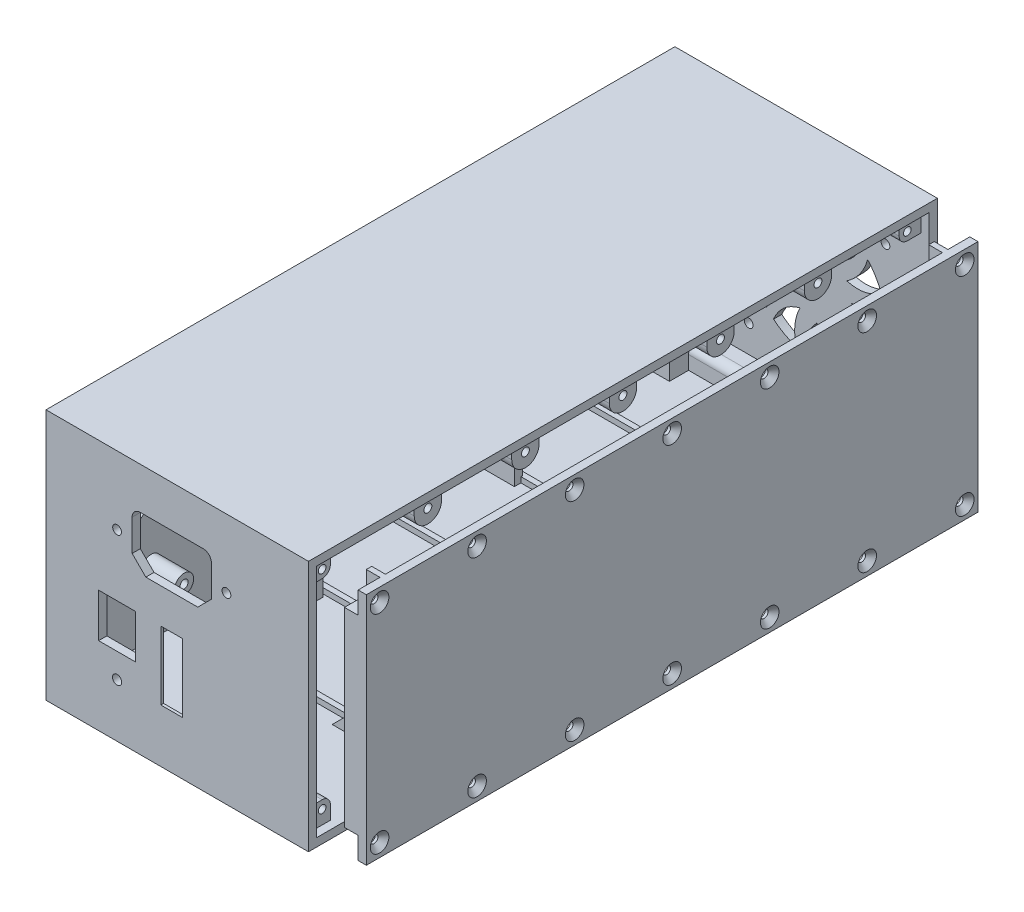
SolidWorks part; units mm, degrees
ref_plane "Front Plane" through (0, 0, 0) normal (0, 0, 1) x (1, 0, 0)
ref_plane "Top Plane" through (0, 0, 0) normal (0, 1, 0) x (1, 0, 0)
ref_plane "Right Plane" through (0, 0, 0) normal (1, 0, 0) x (0, 0, -1)
sketch "Sketch1" plane through (0, 0, 0) normal (1, 0, 0) x (0, 0, -1)
  line L1 (115, 46) -> (-115, 46)
  line L2 (115, 46) -> (115, -46)
  line L3 (115, -46) -> (-115, -46)
  line L4 (-115, 46) -> (-115, -46)
  line L5 (115, 46) -> (-115, -46) construction
  line L6 (115, -46) -> (-115, 46) construction
  point P0 (0, 0)
  dimension "D1" = 92
  dimension "D2" = 230
extrude "Boss-Extrude1" add sketch "Sketch1" along normal blind 3
sketch "Sketch2" plane through (3, 0, 0) normal (1, 0, 0) x (0, 0, -1)
  line L0 (-112, 43) -> (-112, -43)
  line L1 (-112, -43) -> (112, -43)
  line L2 (112, -43) -> (112, 43)
  line L3 (112, 43) -> (-112, 43)
  line L4 (-115, 46) -> (-115, -46)
  line L5 (-115, -46) -> (115, -46)
  line L6 (115, -46) -> (115, 46)
  line L7 (115, 46) -> (-115, 46)
  line L8 (-115, 46) -> (-115, -46)
  line L9 (-115, -46) -> (115, -46)
  line L10 (115, -46) -> (115, 46)
  line L11 (115, 46) -> (-115, 46)
  dimension "D1" = 0
  dimension "D2" = 3
extrude "Boss-Extrude2" add sketch "Sketch2" along normal blind 93
sketch "Sketch3" plane through (0, 0, 0) normal (-1, 0, 0) x (0, 0, 1)
  line L0 (-115, 0) -> (115, 0) construction
  line L1 (-115, -46) -> (-115, 46) construction
  line L2 (115, 46) -> (115, -46) construction
  line L3 (0, 46) -> (0, -46) construction
  line L4 (-115, 46) -> (115, 46) construction
  line L5 (115, -46) -> (-115, -46) construction
  line L6 (26.5, -7.75) -> (18.5, -7.75)
  line L7 (11.5, 7.75) -> (3.5, 7.75)
  line L8 (11.5, 7.75) -> (11.5, -7.75)
  line L9 (11.5, -7.75) -> (3.5, -7.75)
  line L10 (3.5, 7.75) -> (3.5, -7.75)
  line L11 (11.5, 7.75) -> (3.5, -7.75) construction
  line L12 (11.5, -7.75) -> (3.5, 7.75) construction
  line L13 (26.5, 7.75) -> (26.5, -7.75)
  line L14 (26.5, 7.75) -> (18.5, 7.75)
  line L15 (18.5, 7.75) -> (18.5, -7.75)
  line L16 (41.5, -7.75) -> (33.5, -7.75)
  line L17 (41.5, 7.75) -> (41.5, -7.75)
  line L18 (41.5, 7.75) -> (33.5, 7.75)
  line L19 (33.5, 7.75) -> (33.5, -7.75)
  line L20 (56.5, -7.75) -> (48.5, -7.75)
  line L21 (56.5, 7.75) -> (56.5, -7.75)
  line L22 (56.5, 7.75) -> (48.5, 7.75)
  line L23 (48.5, 7.75) -> (48.5, -7.75)
  line L24 (71.5, -7.75) -> (63.5, -7.75)
  line L25 (71.5, 7.75) -> (71.5, -7.75)
  line L26 (71.5, 7.75) -> (63.5, 7.75)
  line L27 (63.5, 7.75) -> (63.5, -7.75)
  line L28 (11.5, -7.75) -> (3.5, -7.75)
  line L29 (11.5, 7.75) -> (11.5, -7.75)
  line L30 (11.5, 7.75) -> (3.5, 7.75)
  line L31 (3.5, 7.75) -> (3.5, -7.75)
  line L32 (26.5, -7.75) -> (18.5, -7.75)
  line L33 (26.5, 7.75) -> (26.5, -7.75)
  line L34 (26.5, 7.75) -> (18.5, 7.75)
  line L35 (18.5, 7.75) -> (18.5, -7.75)
  line L36 (41.5, -7.75) -> (33.5, -7.75)
  line L37 (41.5, 7.75) -> (41.5, -7.75)
  line L38 (41.5, 7.75) -> (33.5, 7.75)
  line L39 (33.5, 7.75) -> (33.5, -7.75)
  line L40 (56.5, -7.75) -> (48.5, -7.75)
  line L41 (56.5, 7.75) -> (56.5, -7.75)
  line L42 (56.5, 7.75) -> (48.5, 7.75)
  line L43 (48.5, 7.75) -> (48.5, -7.75)
  line L44 (-3.5, -7.75) -> (-11.5, -7.75)
  line L45 (-3.5, 7.75) -> (-3.5, -7.75)
  line L46 (-3.5, 7.75) -> (-11.5, 7.75)
  line L47 (-11.5, 7.75) -> (-11.5, -7.75)
  line L48 (11.5, -7.75) -> (3.5, -7.75)
  line L49 (11.5, 7.75) -> (11.5, -7.75)
  line L50 (11.5, 7.75) -> (3.5, 7.75)
  line L51 (3.5, 7.75) -> (3.5, -7.75)
  line L52 (26.5, -7.75) -> (18.5, -7.75)
  line L53 (26.5, 7.75) -> (26.5, -7.75)
  line L54 (26.5, 7.75) -> (18.5, 7.75)
  line L55 (18.5, 7.75) -> (18.5, -7.75)
  line L56 (41.5, -7.75) -> (33.5, -7.75)
  line L57 (41.5, 7.75) -> (41.5, -7.75)
  line L58 (41.5, 7.75) -> (33.5, 7.75)
  line L59 (33.5, 7.75) -> (33.5, -7.75)
  line L60 (-18.5, -7.75) -> (-26.5, -7.75)
  line L61 (-18.5, 7.75) -> (-18.5, -7.75)
  line L62 (-18.5, 7.75) -> (-26.5, 7.75)
  line L63 (-26.5, 7.75) -> (-26.5, -7.75)
  line L64 (-3.5, -7.75) -> (-11.5, -7.75)
  line L65 (-3.5, 7.75) -> (-3.5, -7.75)
  line L66 (-3.5, 7.75) -> (-11.5, 7.75)
  line L67 (-11.5, 7.75) -> (-11.5, -7.75)
  line L68 (11.5, -7.75) -> (3.5, -7.75)
  line L69 (11.5, 7.75) -> (11.5, -7.75)
  line L70 (11.5, 7.75) -> (3.5, 7.75)
  line L71 (3.5, 7.75) -> (3.5, -7.75)
  line L72 (26.5, -7.75) -> (18.5, -7.75)
  line L73 (26.5, 7.75) -> (26.5, -7.75)
  line L74 (26.5, 7.75) -> (18.5, 7.75)
  line L75 (18.5, 7.75) -> (18.5, -7.75)
  line L76 (-33.5, -7.75) -> (-41.5, -7.75)
  line L77 (-33.5, 7.75) -> (-33.5, -7.75)
  line L78 (-33.5, 7.75) -> (-41.5, 7.75)
  line L79 (-41.5, 7.75) -> (-41.5, -7.75)
  line L80 (-18.5, -7.75) -> (-26.5, -7.75)
  line L81 (-18.5, 7.75) -> (-18.5, -7.75)
  line L82 (-18.5, 7.75) -> (-26.5, 7.75)
  line L83 (-26.5, 7.75) -> (-26.5, -7.75)
  line L84 (-3.5, -7.75) -> (-11.5, -7.75)
  line L85 (-3.5, 7.75) -> (-3.5, -7.75)
  line L86 (-3.5, 7.75) -> (-11.5, 7.75)
  line L87 (-11.5, 7.75) -> (-11.5, -7.75)
  line L88 (11.5, -7.75) -> (3.5, -7.75)
  line L89 (11.5, 7.75) -> (11.5, -7.75)
  line L90 (11.5, 7.75) -> (3.5, 7.75)
  line L91 (3.5, 7.75) -> (3.5, -7.75)
  line L92 (-48.5, -7.75) -> (-56.5, -7.75)
  line L93 (-48.5, 7.75) -> (-48.5, -7.75)
  line L94 (-48.5, 7.75) -> (-56.5, 7.75)
  line L95 (-56.5, 7.75) -> (-56.5, -7.75)
  line L96 (-33.5, -7.75) -> (-41.5, -7.75)
  line L97 (-33.5, 7.75) -> (-33.5, -7.75)
  line L98 (-33.5, 7.75) -> (-41.5, 7.75)
  line L99 (-41.5, 7.75) -> (-41.5, -7.75)
  line L100 (-18.5, -7.75) -> (-26.5, -7.75)
  line L101 (-18.5, 7.75) -> (-18.5, -7.75)
  line L102 (-18.5, 7.75) -> (-26.5, 7.75)
  line L103 (-26.5, 7.75) -> (-26.5, -7.75)
  line L104 (-3.5, -7.75) -> (-11.5, -7.75)
  line L105 (-3.5, 7.75) -> (-3.5, -7.75)
  line L106 (-3.5, 7.75) -> (-11.5, 7.75)
  line L107 (-11.5, 7.75) -> (-11.5, -7.75)
  line L108 (-3.5, -7.75) -> (-11.5, -7.75)
  line L109 (-3.5, 7.75) -> (-3.5, -7.75)
  line L110 (-3.5, 7.75) -> (-11.5, 7.75)
  line L111 (-11.5, 7.75) -> (-11.5, -7.75)
  line L112 (-18.5, -7.75) -> (-26.5, -7.75)
  line L113 (-18.5, 7.75) -> (-18.5, -7.75)
  line L114 (-18.5, 7.75) -> (-26.5, 7.75)
  line L115 (-26.5, 7.75) -> (-26.5, -7.75)
  line L116 (-33.5, -7.75) -> (-41.5, -7.75)
  line L117 (-33.5, 7.75) -> (-33.5, -7.75)
  line L118 (-33.5, 7.75) -> (-41.5, 7.75)
  line L119 (-41.5, 7.75) -> (-41.5, -7.75)
  line L120 (-48.5, -7.75) -> (-56.5, -7.75)
  line L121 (-48.5, 7.75) -> (-48.5, -7.75)
  line L122 (-48.5, 7.75) -> (-56.5, 7.75)
  line L123 (-56.5, 7.75) -> (-56.5, -7.75)
  line L124 (-63.5, -7.75) -> (-71.5, -7.75)
  line L125 (-63.5, 7.75) -> (-63.5, -7.75)
  line L126 (-63.5, 7.75) -> (-71.5, 7.75)
  line L127 (-71.5, 7.75) -> (-71.5, -7.75)
  circle A0 centre (84.6037, 0) radius 1
  point P12 (7.5, 0)
  dimension "D6" = 2
  dimension "D1" = 7.5
  dimension "D2" = 15.5
  dimension "D3" = 8
  dimension "D4" = 5
  dimension "D5" = 6
extrude "Cut-Extrude1" cut sketch "Sketch3" against normal up to surface (3 mm away) contours L126 L127 L124 L125 | L94 L95 L92 L93 | L78 L79 L76 L77 | L62 L63 L60 L61 | L46 L47 L44 L45 | L7 L10 L9 L8 | L14 L15 L6 L13 | L18 L19 L16 L17 | L22 L23 L20 L21 | L26 L27 L24 L25 | A0 region at (0, 0, 22.5) region at (0, 0, 7.5) region at (0, 0, 37.5) region at (0, 0, 52.5) region at (0, 0, 67.5) region at (0, 0, -7.5) region at (0, 0, -22.5) region at (0, 0, -37.5) region at (0, 0, -52.5) region at (0, 0, -67.5) region at (0, 0, 84.6037) up to face at (3, 0, 0)
sketch "Sketch4" plane through (96, 0, 0) normal (1, 0, 0) x (0, 0, -1)
  line L0 (0, 43) -> (0, -43) construction
  line L1 (112, 43) -> (-112, 43) construction
  line L2 (-112, -43) -> (112, -43) construction
  line L3 (-112, 43) -> (-112, -43) construction
  line L4 (-104, 38) -> (-104, 43)
  line L5 (-104, 43) -> (-112, 43)
  line L6 (-112, 43) -> (-112, 35)
  line L7 (-112, 35) -> (-107, 35)
  line L8 (0, 0) -> (-112, 0) construction
  line L9 (-107, -35) -> (-112, -35)
  line L10 (-112, 43) -> (-112, -43) construction
  line L11 (-112, -35) -> (-112, -43)
  line L12 (-104, -38) -> (-104, -43)
  line L13 (-104, -43) -> (-112, -43)
  line L14 (104, -43) -> (112, -43)
  line L15 (112, -35) -> (112, -43)
  line L16 (107, -35) -> (112, -35)
  line L17 (112, 35) -> (107, 35)
  line L18 (112, 43) -> (112, 35)
  line L19 (104, 43) -> (112, 43)
  line L20 (104, 38) -> (104, 43)
  line L21 (104, -38) -> (104, -43)
  circle A0 centre (-107, 38) radius 1.4
  circle A1 centre (-107, -38) radius 1.4
  arc A2 (-104, 38) -> (-107, 35) centre (-107, 38) cw
  arc A3 (-107, -35) -> (-104, -38) centre (-107, -38) cw
  arc A4 (107, -35) -> (104, -38) centre (107, -38) ccw
  circle A5 centre (107, -38) radius 1.4
  arc A6 (104, 38) -> (107, 35) centre (107, 38) ccw
  circle A7 centre (107, 38) radius 1.4
  dimension "D5" = 2.8
  dimension "D6" = 3
  dimension "D1" = 5
  dimension "D2" = 5
  dimension "D3" = 5
  dimension "D4" = 5
extrude "Boss-Extrude3" add sketch "Sketch4" against normal up to surface (93 mm away) from offset 3 up to face at (3, 0, -67.5) offset against normal yes
sketch "Sketch5" plane through (93, 0, 0) normal (1, 0, 0) x (0, 0, -1)
  circle A0 centre (-107, -38) radius 1.4 construction
  circle A1 centre (107, -38) radius 1.4 construction
  circle A2 centre (107, 38) radius 1.4 construction
  circle A3 centre (-107, 38) radius 1.4 construction
  circle A4 centre (-107, -38) radius 1.4
  circle A5 centre (107, -38) radius 1.4
  circle A6 centre (107, 38) radius 1.4
  circle A7 centre (-107, 38) radius 1.4
extrude "Boss-Extrude4" add sketch "Sketch5" against normal up to surface (90 mm away) from offset 20 up to face at (3, 0, -67.5) offset against normal yes
sketch "Sketch6" plane through (0, 0, 115) normal (0, 0, 1) x (1, 0, 0)
  line L0 (46, 46) -> (46, -46) construction
  line L1 (96, 46) -> (0, 46) construction
  line L2 (96, -46) -> (0, -46) construction
  line L3 (93, 43) -> (93, 38) construction
  line L4 (79.2275, 21) -> (12.7725, 21) construction
  line L5 (36.5, 11.25) -> (31.5, 16.25)
  line L6 (57.5, 30.75) -> (34.5, 30.75)
  line L7 (60.5, 27.75) -> (60.5, 16.25)
  line L8 (55.5, 11.25) -> (36.5, 11.25)
  line L9 (31.5, 27.75) -> (31.5, 16.25)
  line L10 (60.5, 30.75) -> (31.5, 11.25) construction
  line L11 (60.5, 11.25) -> (31.5, 30.75) construction
  line L12 (60.5, 16.25) -> (55.5, 11.25)
  line L14 (50, -1.5) -> (42, -1.5)
  line L15 (50, -1.5) -> (50, -26.5)
  line L16 (50, -26.5) -> (42, -26.5)
  line L17 (42, -1.5) -> (42, -26.5)
  line L18 (50, -1.5) -> (42, -26.5) construction
  line L19 (50, -26.5) -> (42, -1.5) construction
  line L20 (32.75, -1.5) -> (19.25, -1.5)
  line L21 (32.75, -1.5) -> (32.75, -17.5)
  line L22 (32.75, -17.5) -> (19.25, -17.5)
  line L23 (19.25, -1.5) -> (19.25, -17.5)
  line L24 (32.75, -1.5) -> (19.25, -17.5) construction
  line L25 (32.75, -17.5) -> (19.25, -1.5) construction
  circle A2 centre (26, 21) radius 1.6
  circle A3 centre (66, 21) radius 1.6
  arc A4 (57.5, 30.75) -> (60.5, 27.75) centre (57.5, 27.75) cw
  arc A5 (34.5, 30.75) -> (31.5, 27.75) centre (34.5, 27.75) ccw
  circle A6 centre (26, -26.5) radius 1.7
  point P11 (46, 21)
  point P15 (46, 21)
  point P30 (46, -14)
  point P35 (26, -9.5)
  dimension "D2" = 3.2
  dimension "D7" = 3
  dimension "D1" = 47
  dimension "D3" = 20
  dimension "D4" = 20
  dimension "D5" = 29
  dimension "D6" = 19.5
  dimension "D8" = 25
  dimension "D9" = 8
  dimension "D10" = 25
  dimension "D13" = 32
  dimension "D14" = 20
  dimension "D15" = 13.5
  dimension "D16" = 16
extrude "Cut-Extrude2" cut sketch "Sketch6" against normal up to surface (3 mm away) up to face at (71.25, 0, 112)
sketch "Sketch7" plane through (0, 0, 112) normal (0, 0, -1) x (-1, 0, 0)
  line L0 (-39.5, 6) -> (-39.5, -32.5)
  line L1 (-39.5, -32.5) -> (-52, -32.5)
  line L2 (-52, -32.5) -> (-52, 6)
  line L3 (-52, 6) -> (-39.5, 6)
  line L4 (-50, -1.5) -> (-42, -1.5) construction
  line L5 (-50, -26.5) -> (-50, -1.5) construction
  dimension "D1" = 7.5
  dimension "D2" = 2
  dimension "D3" = 38.5
  dimension "D4" = 12.5
extrude "Cut-Extrude3" cut sketch "Sketch7" against normal blind 2
chamfer "Chamfer1" distance 2 angle 45 1 edges at (52, -13.25, 112)
sketch "Sketch8" plane through (3, 0, 0) normal (1, 0, 0) x (0, 0, -1)
  line L0 (-71.5, 0) -> (91.1958, 0) construction
  line L1 (-71.5, -7.75) -> (-71.5, 7.75) construction
  line L2 (-79.5, 43) -> (-79.5, -43) construction
  line L3 (112, 43) -> (-112, 43) construction
  line L4 (-104, -43) -> (104, -43) construction
  circle A0 centre (-79.5, 19.5) radius 1.5
  circle A1 centre (-79.5, -19.5) radius 1.5
  circle A2 centre (-79.5, 19.5) radius 3.5
  circle A3 centre (-79.5, -19.5) radius 3.5
  circle A4 centre (72, -19.5) radius 1.5
  circle A5 centre (72, -19.5) radius 3.5
  circle A6 centre (72, 19.5) radius 3.5
  circle A7 centre (72, 19.5) radius 1.5
  dimension "D1" = 3
  dimension "D2" = 7
  dimension "D3" = 8
  dimension "D5" = 19.5
  dimension "D6" = 19.5
  dimension "D7" = 19.5
  dimension "D8" = 19.5
  dimension "D9" = 151.5
extrude "Boss-Extrude5" add sketch "Sketch8" along normal blind 12
sketch "Sketch9" plane through (3, 0, 0) normal (1, 0, 0) x (0, 0, -1)
  circle A0 centre (-84.6037, 0) radius 3
extrude "Cut-Extrude4" cut sketch "Sketch9" against normal blind 2.2
ref_plane "Plane1" through (106, 0, 0) normal (1, 0, 0) x (0, 0, -1)
sketch "Sketch10" plane through (106, 0, 0) normal (1, 0, 0) x (0, 0, -1)
  line L112 (107, -32.85) -> (109.85, -32.85)
  line L113 (109.85, -32.85) -> (109.85, 32.85)
  line L114 (109.85, 32.85) -> (107, 32.85)
  line L115 (101.85, 38) -> (101.85, 40.85)
  line L116 (101.85, 40.85) -> (-101.85, 40.85)
  line L117 (-101.85, 40.85) -> (-101.85, 38)
  line L118 (-107, 32.85) -> (-109.85, 32.85)
  line L119 (-109.85, 32.85) -> (-109.85, -32.85)
  line L120 (-109.85, -32.85) -> (-107, -32.85)
  line L121 (-101.85, -38) -> (-101.85, -40.85)
  line L122 (-101.85, -40.85) -> (101.85, -40.85)
  line L123 (101.85, -40.85) -> (101.85, -38)
  line L124 (107, -34.85) -> (111.85, -34.85)
  line L125 (103.85, -42.85) -> (103.85, -38)
  line L126 (-103.85, -42.85) -> (103.85, -42.85)
  line L127 (-103.85, -38) -> (-103.85, -42.85)
  line L128 (-111.85, -34.85) -> (-107, -34.85)
  line L129 (-111.85, 34.85) -> (-111.85, -34.85)
  line L130 (-107, 34.85) -> (-111.85, 34.85)
  line L131 (-103.85, 42.85) -> (-103.85, 38)
  line L132 (103.85, 42.85) -> (-103.85, 42.85)
  line L133 (103.85, 38) -> (103.85, 42.85)
  line L134 (111.85, 34.85) -> (107, 34.85)
  line L135 (111.85, -34.85) -> (111.85, 34.85)
  line L136 (107, -34.85) -> (111.85, -34.85)
  line L137 (103.85, -42.85) -> (103.85, -38)
  line L138 (-103.85, -42.85) -> (103.85, -42.85)
  line L139 (-103.85, -38) -> (-103.85, -42.85)
  line L140 (-111.85, -34.85) -> (-107, -34.85)
  line L141 (-111.85, 34.85) -> (-111.85, -34.85)
  line L142 (-107, 34.85) -> (-111.85, 34.85)
  line L143 (-103.85, 42.85) -> (-103.85, 38)
  line L144 (103.85, 42.85) -> (-103.85, 42.85)
  line L145 (103.85, 38) -> (103.85, 42.85)
  line L146 (111.85, 34.85) -> (107, 34.85)
  line L147 (111.85, -34.85) -> (111.85, 34.85)
  arc A36 (107, -34.85) -> (103.85, -38) centre (107, -38) ccw
  arc A37 (-103.85, -38) -> (-107, -34.85) centre (-107, -38) ccw
  arc A38 (-107, 34.85) -> (-103.85, 38) centre (-107, 38) ccw
  arc A39 (103.85, 38) -> (107, 34.85) centre (107, 38) ccw
  arc A40 (107, -34.85) -> (103.85, -38) centre (107, -38) ccw
  arc A41 (-103.85, -38) -> (-107, -34.85) centre (-107, -38) ccw
  arc A42 (-107, 34.85) -> (-103.85, 38) centre (-107, 38) ccw
  arc A43 (103.85, 38) -> (107, 34.85) centre (107, 38) ccw
  arc A48 (101.85, 38) -> (107, 32.85) centre (107, 38) ccw
  arc A49 (-107, 32.85) -> (-101.85, 38) centre (-107, 38) ccw
  arc A50 (-101.85, -38) -> (-107, -32.85) centre (-107, -38) ccw
  arc A51 (107, -32.85) -> (101.85, -38) centre (107, -38) ccw
  dimension "D1" = 0.15
  dimension "D2" = 2
extrude "Boss-Extrude6" add sketch "Sketch10" along normal blind 5 separate body
sketch "Sketch11" plane through (111, 0, 0) normal (1, 0, 0) x (0, 0, -1)
  line L0 (111.85, -34.85) -> (111.85, 34.85) construction
  line L1 (-103.85, -42.85) -> (103.85, -42.85) construction
  line L2 (-111.85, 34.85) -> (-111.85, -34.85) construction
  line L3 (103.85, 42.85) -> (-103.85, 42.85) construction
  line L4 (111.85, -34.85) -> (111.85, 34.85)
  line L5 (-103.85, -42.85) -> (103.85, -42.85)
  line L6 (-111.85, 34.85) -> (-111.85, -34.85)
  line L7 (103.85, 42.85) -> (-103.85, 42.85)
  line L8 (103.85, 42.85) -> (111.85, 42.85)
  line L9 (111.85, 42.85) -> (111.85, 34.85)
  line L10 (111.85, -34.85) -> (111.85, -42.85)
  line L11 (111.85, -42.85) -> (103.85, -42.85)
  line L12 (-111.85, -34.85) -> (-111.85, -42.85)
  line L13 (-111.85, -42.85) -> (-103.85, -42.85)
  line L14 (-103.85, 42.85) -> (-111.85, 42.85)
  line L15 (-111.85, 42.85) -> (-111.85, 34.85)
  circle A0 centre (-107, -38) radius 1.4 construction
  circle A1 centre (107, -38) radius 1.4 construction
  circle A2 centre (107, 38) radius 1.4 construction
  circle A3 centre (-107, 38) radius 1.4 construction
  circle A4 centre (-107, -38) radius 1.4
  circle A5 centre (107, -38) radius 1.4
  circle A6 centre (107, 38) radius 1.4
  circle A7 centre (-107, 38) radius 1.4
extrude "Boss-Extrude7" add sketch "Sketch11" along normal blind 3
sketch "Sketch12" plane through (114, 0, 0) normal (1, 0, 0) x (0, 0, -1)
  line L0 (-112, 0) -> (111.85, 0) construction
  line L1 (89, 29.25) -> (-89, 29.25) construction
  line L2 (89, 29.25) -> (89, -29.25) construction
  line L3 (89, -29.25) -> (-89, -29.25) construction
  line L4 (-89, 29.25) -> (-89, -29.25) construction
  line L5 (89, 29.25) -> (-89, -29.25) construction
  line L6 (89, -29.25) -> (-89, 29.25) construction
  line L7 (-112, 43) -> (-112, -43) construction
  line L8 (111.85, -42.85) -> (111.85, 42.85) construction
  circle A0 centre (-89, 29.25) radius 1.8
  circle A1 centre (-89, -29.25) radius 1.8
  circle A2 centre (89, -29.25) radius 1.8
  circle A3 centre (89, 29.25) radius 1.8
  circle A4 centre (-47.3819, 9) radius 1.8
  circle A5 centre (26.6181, 9) radius 1.8
  circle A6 centre (-4.3819, 9) radius 1.8
  circle A7 centre (-4.3819, -9) radius 1.8
  point P0 (0, 0)
  dimension "D3" = 3.6
  dimension "D10" = 3.6
  dimension "D1" = 58.5
  dimension "D2" = 178
  dimension "D4" = 9
  dimension "D5" = 9
  dimension "D6" = 74
  dimension "D7" = 31
  dimension "D8" = 9
  dimension "D9" = 9
sketch "Sketch13" plane through (96, 0, 0) normal (1, 0, 0) x (0, 0, -1)
  line L12 (104, 38) -> (104, 43)
  line L13 (104, 43) -> (-104, 43)
  line L14 (-104, 43) -> (-104, 38)
  line L15 (-107, 35) -> (-112, 35)
  line L16 (-112, 35) -> (-112, -35)
  line L17 (-112, -35) -> (-107, -35)
  line L18 (-104, -38) -> (-104, -43)
  line L19 (-104, -43) -> (104, -43)
  line L20 (104, -43) -> (104, -38)
  line L21 (107, -35) -> (112, -35)
  line L22 (112, -35) -> (112, 35)
  line L23 (112, 35) -> (107, 35)
  line L24 (104, 38) -> (104, 43)
  line L25 (104, 43) -> (-104, 43)
  line L26 (-104, 43) -> (-104, 38)
  line L27 (-107, 35) -> (-112, 35)
  line L28 (-112, 35) -> (-112, -35)
  line L29 (-112, -35) -> (-107, -35)
  line L30 (-104, -38) -> (-104, -43)
  line L31 (-104, -43) -> (104, -43)
  line L32 (104, -43) -> (104, -38)
  line L33 (107, -35) -> (112, -35)
  line L34 (112, -35) -> (112, 35)
  line L35 (112, 35) -> (107, 35)
  arc A4 (104, 38) -> (107, 35) centre (107, 38) ccw
  arc A5 (-107, 35) -> (-104, 38) centre (-107, 38) ccw
  arc A6 (-104, -38) -> (-107, -35) centre (-107, -38) ccw
  arc A7 (107, -35) -> (104, -38) centre (107, -38) ccw
  arc A8 (104, 38) -> (107, 35) centre (107, 38) ccw
  arc A9 (-107, 35) -> (-104, 38) centre (-107, 38) ccw
  arc A10 (-104, -38) -> (-107, -35) centre (-107, -38) ccw
  arc A11 (107, -35) -> (104, -38) centre (107, -38) ccw
  dimension "D1" = 0
sketch "Sketch14" plane through (93, 0, 0) normal (1, 0, 0) x (0, 0, -1)
  line L0 (-68.334, -43) -> (-68.334, -41)
  line L2 (-104, -43) -> (-104, -38) construction
  line L3 (-68.334, 43) -> (-68.334, 41)
  line L5 (-104, 38) -> (-104, 43) construction
  dimension "D1" = 35.666
  dimension "D2" = 35.666
extrude "Extrude-Thin2" add sketch "Sketch14" against normal up to surface (90 mm away) from offset 3 thin up to face at (3, 0, 81.6037) offset against normal yes thin type mid plane wall 2
pattern_linear "LPattern1" count 5 spacing 35.666 along (0, 0, -1) of "Extrude-Thin2"
sketch "Sketch15" plane through (3, 40, 0) normal (1, 0, 0) x (0, 1, 0)
  line L0 (-40, 112) -> (-40, -112.6115) construction
  line L2 (-5, 112) -> (-75, 112) construction
  line L3 (-13.5, 36.1943) -> (-66.5, 36.1943) construction
  line L4 (-13.5, 36.1943) -> (-13.5, -36.8057) construction
  line L5 (-13.5, -36.8057) -> (-66.5, -36.8057) construction
  line L6 (-66.5, 36.1943) -> (-66.5, -36.8057) construction
  line L7 (-13.5, 36.1943) -> (-66.5, -36.8057) construction
  line L8 (-13.5, -36.8057) -> (-66.5, 36.1943) construction
  circle A0 centre (-13.5, 36.1943) radius 1.25
  circle A1 centre (-66.5, 36.1943) radius 1.25
  circle A2 centre (-66.5, -36.8057) radius 1.25
  circle A4 centre (-66.5, 36.1943) radius 2.5
  circle A5 centre (-13.5, 36.1943) radius 2.5
  circle A7 centre (-66.5, -36.8057) radius 2.5
  circle A8 centre (-13.5, -36.8057) radius 1.25
  circle A9 centre (-13.5, -36.8057) radius 2.5
  point P4 (-40, -0.3057)
  point P20 (-40, 112)
  dimension "D3" = 2.5
  dimension "D4" = 5
  dimension "D1" = 53
  dimension "D2" = 73
extrude "Boss-Extrude9" add sketch "Sketch15" along normal blind 20
sketch "Sketch16" plane through (0, 0, -112) normal (0, 0, 1) x (1, 0, 0)
  line L0 (3, 0) -> (96, 0) construction
  line L1 (3, -35) -> (3, 35) construction
  line L3 (55, 0) -> (67.5, 0) construction
  line L4 (80, 25) -> (30, 25) construction
  line L5 (80, 25) -> (80, -25) construction
  line L6 (80, -25) -> (30, -25) construction
  line L7 (30, 25) -> (30, -25) construction
  line L8 (80, 25) -> (30, -25) construction
  line L9 (80, -25) -> (30, 25) construction
  line L10 (55, 0) -> (65.8253, -6.25) construction
  line L11 (96, -35) -> (96, 35) construction
  circle A0 centre (30, 25) radius 1.6
  circle A1 centre (80, 25) radius 1.6
  circle A2 centre (80, -25) radius 1.6
  circle A3 centre (30, -25) radius 1.6
  circle A4 centre (55, 0) radius 12.5 construction
  arc A5 (79.4256, 5.3285) -> (79.6515, -4.1595) centre (55, 0) cw
  arc A6 (78.8174, -7.5982) -> (74.2691, -15.928) centre (55, 0) cw
  arc A7 (71.8274, -18.4889) -> (63.7236, -23.4286) centre (55, 0) cw
  arc A8 (60.3285, -24.4256) -> (50.8405, -24.6515) centre (55, 0) cw
  arc A9 (47.4018, -23.8174) -> (39.072, -19.2691) centre (55, 0) cw
  arc A10 (36.5111, -16.8274) -> (31.5714, -8.7236) centre (55, 0) cw
  arc A11 (30.5744, -5.3285) -> (30.3485, 4.1595) centre (55, 0) cw
  arc A12 (31.1826, 7.5982) -> (35.7309, 15.928) centre (55, 0) cw
  arc A13 (38.1726, 18.4889) -> (46.2764, 23.4286) centre (55, 0) cw
  arc A14 (49.6715, 24.4256) -> (59.1595, 24.6515) centre (55, 0) cw
  arc A15 (62.5982, 23.8174) -> (70.928, 19.2691) centre (55, 0) cw
  arc A16 (73.4889, 16.8274) -> (78.4286, 8.7236) centre (55, 0) cw
  spline S0 degree 2 poles (79.4256, 5.3285) (74.5238, 0.5174) (67.5, 0) knots 0 0 0 1 1 1
  spline S1 degree 2 poles (67.5, 0) (72.6575, -5.0815) (79.6515, -4.1595) knots 0 0 0 1 1 1
  spline S2 degree 2 poles (78.8174, -7.5982) (72.1668, -9.3138) (65.8253, -6.25) knots 0 0 0 1 1 1
  spline S3 degree 2 poles (65.8253, -6.25) (67.7511, -13.2294) (74.2691, -15.928) knots 0 0 0 1 1 1
  spline S4 degree 2 poles (71.8274, -18.4889) (65.21, -16.6494) (61.25, -10.8253) knots 0 0 0 1 1 1
  spline S5 degree 2 poles (61.25, -10.8253) (59.428, -17.8326) (63.7236, -23.4286) knots 0 0 0 1 1 1
  spline S6 degree 2 poles (60.3285, -24.4256) (55.5174, -19.5238) (55, -12.5) knots 0 0 0 1 1 1
  spline S7 degree 2 poles (55, -12.5) (49.9185, -17.6575) (50.8405, -24.6515) knots 0 0 0 1 1 1
  spline S8 degree 2 poles (47.4018, -23.8174) (45.6862, -17.1668) (48.75, -10.8253) knots 0 0 0 1 1 1
  spline S9 degree 2 poles (48.75, -10.8253) (41.7706, -12.7511) (39.072, -19.2691) knots 0 0 0 1 1 1
  spline S10 degree 2 poles (36.5111, -16.8274) (38.3506, -10.21) (44.1747, -6.25) knots 0 0 0 1 1 1
  spline S11 degree 2 poles (44.1747, -6.25) (37.1674, -4.428) (31.5714, -8.7236) knots 0 0 0 1 1 1
  spline S12 degree 2 poles (30.5744, -5.3285) (35.4762, -0.5174) (42.5, 0) knots 0 0 0 1 1 1
  spline S13 degree 2 poles (42.5, 0) (37.3425, 5.0815) (30.3485, 4.1595) knots 0 0 0 1 1 1
  spline S14 degree 2 poles (31.1826, 7.5982) (37.8332, 9.3138) (44.1747, 6.25) knots 0 0 0 1 1 1
  spline S15 degree 2 poles (44.1747, 6.25) (42.2489, 13.2294) (35.7309, 15.928) knots 0 0 0 1 1 1
  spline S16 degree 2 poles (38.1726, 18.4889) (44.79, 16.6494) (48.75, 10.8253) knots 0 0 0 1 1 1
  spline S17 degree 2 poles (48.75, 10.8253) (50.572, 17.8326) (46.2764, 23.4286) knots 0 0 0 1 1 1
  spline S18 degree 2 poles (49.6715, 24.4256) (54.4826, 19.5238) (55, 12.5) knots 0 0 0 1 1 1
  spline S19 degree 2 poles (55, 12.5) (60.0815, 17.6575) (59.1595, 24.6515) knots 0 0 0 1 1 1
  spline S20 degree 2 poles (62.5982, 23.8174) (64.3138, 17.1668) (61.25, 10.8253) knots 0 0 0 1 1 1
  spline S21 degree 2 poles (61.25, 10.8253) (68.2294, 12.7511) (70.928, 19.2691) knots 0 0 0 1 1 1
  spline S22 degree 2 poles (73.4889, 16.8274) (71.6494, 10.21) (65.8253, 6.25) knots 0 0 0 1 1 1
  spline S23 degree 2 poles (65.8253, 6.25) (72.8326, 4.428) (78.4286, 8.7236) knots 0 0 0 1 1 1
  point P6 (55, 0)
  point P83 (96, 0)
  dimension "D4" = 3.2
  dimension "D5" = 25
  dimension "D6" = 12
  dimension "D1" = 50
  dimension "D2" = 50
  dimension "D7" = 30
extrude "Cut-Extrude6" cut sketch "Sketch16" against normal up to surface (3 mm away) up to face at (48, 0, -115)
sketch "Sketch17" plane through (111, 0, 0) normal (-1, 0, 0) x (0, 0, 1)
  line L0 (-109.85, -0.85) -> (109.85, -0.85) construction
  line L1 (-109.85, -32.85) -> (-109.85, 32.85) construction
  line L2 (109.85, 32.85) -> (109.85, -32.85) construction
  line L3 (101.85, -40.85) -> (-101.85, -40.85) construction
  line L4 (-8.5, 20.1) -> (-91.2, 20.1) construction
  line L5 (-8.5, 20.1) -> (-8.5, -21.8) construction
  line L6 (-8.5, -21.8) -> (-91.2, -21.8) construction
  line L7 (-91.2, 20.1) -> (-91.2, -21.8) construction
  line L8 (-8.5, 20.1) -> (-91.2, -21.8) construction
  line L9 (-8.5, -21.8) -> (-91.2, 20.1) construction
  line L10 (79.15, 12.15) -> (21.15, 12.15) construction
  line L11 (79.15, 12.15) -> (79.15, -13.85) construction
  line L12 (79.15, -13.85) -> (21.15, -13.85) construction
  line L13 (21.15, 12.15) -> (21.15, -13.85) construction
  line L14 (79.15, 12.15) -> (21.15, -13.85) construction
  line L15 (79.15, -13.85) -> (21.15, 12.15) construction
  line L16 (-109.85, -32.85) -> (-109.85, 32.85) construction
  circle A0 centre (-91.2, 20.1) radius 1.4
  circle A1 centre (-91.2, -21.8) radius 1.4
  circle A2 centre (-8.5, -21.8) radius 1.4
  circle A3 centre (-8.5, 20.1) radius 1.4
  circle A4 centre (79.15, 12.15) radius 1.4
  circle A5 centre (21.15, 12.15) radius 1.4
  circle A6 centre (21.15, -13.85) radius 1.4
  circle A7 centre (79.15, -13.85) radius 1.4
  circle A8 centre (-91.2, 20.1) radius 3.25
  circle A9 centre (-8.5, 20.1) radius 3.25
  circle A10 centre (-8.5, -21.8) radius 3.25
  circle A11 centre (-91.2, -21.8) radius 3.25
  circle A12 centre (21.15, -13.85) radius 3.25
  circle A13 centre (21.15, 12.15) radius 3.25
  circle A14 centre (79.15, 12.15) radius 3.25
  circle A15 centre (79.15, -13.85) radius 3.25
  point P6 (-49.85, -0.85)
  point P11 (50.15, -0.85)
  dimension "D8" = 2.8
  dimension "D9" = 6.5
  dimension "D1" = 82.7
  dimension "D2" = 41.9
  dimension "D3" = 40
  dimension "D4" = 60
  dimension "D5" = 58
  dimension "D6" = 26
  dimension "D7" = 100
extrude "Boss-Extrude10" add sketch "Sketch17" along normal blind 5
sketch "Sketch18" plane through (93, 0, 0) normal (1, 0, 0) x (0, 0, -1)
  line L0 (74.33, -41) -> (74.33, -35.3123) construction
  line L1 (73.33, -41) -> (75.33, -41) construction
  line L2 (-112, -43) -> (112, -43) construction
  line L3 (69.33, -38) -> (69.33, -43)
  line L5 (69.33, -43) -> (79.33, -43)
  line L6 (79.33, -43) -> (79.33, -38)
  circle A0 centre (74.33, -38) radius 1.45
  arc A1 (69.33, -38) -> (79.33, -38) centre (74.33, -38) cw
  dimension "D1" = 2.9
  dimension "D3" = 5
  dimension "D2" = 5
extrude "Boss-Extrude11" add sketch "Sketch18" against normal blind 20
chamfer "Chamfer3" distance 10 angle 45 1 edges at (73, -43, -71.33)
ref_plane "Plane2" through (0, 0, 0) normal (0, -1, 0) x (-1, 0, 0)
mirror "Mirror4" about plane through (0, 0, 0) normal (0, -1, 0) of "Boss-Extrude11"
chamfer "Chamfer4" distance 10 angle 45 1 edges at (73, 43, -71.33)
pattern_linear "LPattern4" count 5 spacing 35.666 along (0, 0, 1) of "Boss-Extrude11", "Chamfer3", "Mirror4", "Chamfer4"
sketch "Sketch21" plane through (106, 0, 0) normal (-1, 0, 0) x (0, 0, 1)
  line L0 (-101.85, -44.15) -> (-101.85, -36.4687)
  line L1 (-101.85, 40.85) -> (101.8627, 40.85)
  line L2 (-101.85, 40.85) -> (-101.85, 48.5313)
  line L3 (-101.85, 48.5313) -> (101.8627, 48.5313)
  line L4 (101.8627, 40.85) -> (101.8627, 48.5313)
  line L5 (-101.85, -44.15) -> (101.8627, -44.15)
  line L6 (101.8627, -44.15) -> (101.8627, -36.4687)
  line L7 (-101.85, -36.4687) -> (101.8627, -36.4687)
  dimension "D1" = 2
extrude "Cut-Extrude7" cut sketch "Sketch21" against normal up to surface (5 mm away) up to face at (111, -13.85, 82.4)
sketch "Sketch22" plane through (114, 0, 0) normal (1, 0, 0) x (0, 0, -1)
  line L0 (-107, 38) -> (-71.334, 38) construction
  line L1 (-111.85, 0) -> (111.85, 0) construction
  line L2 (-111.85, 42.85) -> (-111.85, -42.85) construction
  line L3 (111.85, -42.85) -> (111.85, 42.85) construction
  circle A0 centre (-71.334, 38) radius 1.4
  circle A1 centre (-107, 38) radius 1.4 construction
  circle A2 centre (-35.668, 38) radius 1.4
  circle A3 centre (-0.002, 38) radius 1.4
  circle A4 centre (35.664, 38) radius 1.4
  circle A5 centre (71.33, 38) radius 1.4
  circle A6 centre (71.33, -38) radius 1.4
  circle A7 centre (35.664, -38) radius 1.4
  circle A8 centre (-0.002, -38) radius 1.4
  circle A9 centre (-35.668, -38) radius 1.4
  circle A10 centre (-71.334, -38) radius 1.4
  dimension "D2" = 35.666
  dimension "D3" = 35.666
  dimension "D1" = 5
extrude "Cut-Extrude8" cut sketch "Sketch22" against normal up to surface (3 mm away) up to face at (111, 4.5559, 11.3264)
chamfer "Chamfer5" distance 2 angle 45 14 edges at (114, -38, 105.6) (114, -38, 72.734) (114, -38, 37.068) (114, -38, 1.402) (114, -38, -34.264) (114, -38, -69.93) (114, -38, -108.4) (114, 38, -37.064) (114, 38, -1.398) (114, 38, 34.268) (114, 38, 105.6) (114, 38, 69.934) (114, 38, -108.4) (114, 38, -72.73)
sketch "Sketch23" plane through (0, 0, -112) normal (0, 0, 1) x (1, 0, 0)
  line L0 (3, 0) -> (96, 0) construction
  line L1 (3, -35) -> (3, 35) construction
  line L2 (96, -43) -> (96, 43) construction
  line L3 (3, 30.1015) -> (3, 43)
  line L4 (3, 43) -> (93, 43) construction
  line L5 (3, -30.1015) -> (3, 30.1015)
  line L6 (3, 43) -> (16, 43)
  line L11 (3, -43) -> (16, -43)
  line L12 (3, -30.1015) -> (3, -43)
  line L13 (16, -43) -> (16, 43)
  circle A0 centre (8, 35.5) radius 1.6
  circle A1 centre (8, -35.5) radius 1.6
  dimension "D1" = 3.2
  dimension "D2" = 5
  dimension "D3" = 71
  dimension "D4" = 13
extrude "Boss-Extrude12" add sketch "Sketch23" along normal blind 15
sketch "Sketch24" plane through (0, 0, 0) normal (-1, 0, 0) x (0, 0, 1)
  line L0 (-115, 0) -> (-89.7581, 0) construction
  line L1 (-115, -46) -> (-115, 46) construction
  line L3 (-101.8, 40.1) -> (-112, 40.1)
  line L4 (-101.8, 40.1) -> (-101.8, -40.1)
  line L5 (-101.8, -40.1) -> (-112, -40.1)
  line L6 (-112, 40.1) -> (-112, -40.1)
  line L7 (-101.8, 40.1) -> (-112, -40.1) construction
  line L8 (-101.8, -40.1) -> (-112, 40.1) construction
  point P5 (-106.9, 0)
  dimension "D1" = 3
  dimension "D2" = 10.2
  dimension "D3" = 80.2
extrude "Cut-Extrude9" cut sketch "Sketch24" against normal blind 13
sketch "Sketch25" plane through (0, 0, -115) normal (0, 0, -1) x (-1, 0, 0)
  circle A0 centre (-8, 35.5) radius 1.6
  circle A1 centre (-8, -35.5) radius 1.6
  dimension "D1" = 3.2
extrude "Cut-Extrude10" cut sketch "Sketch25" against normal up to surface (3 mm away) up to face at (46.3903, -18.8616, -112)
sketch "Sketch26" plane through (23, 0, 0) normal (1, 0, 0) x (0, 0, -1)
  line L1 (53.3288, 25) -> (-53.3288, 25)
  line L2 (53.3288, 25) -> (53.3288, -25)
  line L3 (53.3288, -25) -> (-53.3288, -25)
  line L4 (-53.3288, 25) -> (-53.3288, -25)
  line L5 (53.3288, 25) -> (-53.3288, -25) construction
  line L6 (53.3288, -25) -> (-53.3288, 25) construction
  point P0 (0, 0)
  dimension "D1" = 50
extrude "Cut-Extrude11" cut sketch "Sketch26" against normal up to surface (8 mm away) up to face at (15, 19.5, 76)
ref_plane "Plane3" through (0, 0, 36.1943) normal (0, 0, 1) x (1, 0, 0)
sketch "Sketch27" plane through (0, 0, 36.1943) normal (0, 0, 1) x (1, 0, 0)
  line L0 (21, -29) -> (21, -43)
  line L1 (3, -7.75) -> (3, 7.75) construction
  line L2 (3, -43) -> (16, -43) construction
  line L3 (3, -29) -> (3, -24) construction
  dimension "D1" = 18
rib "Rib12" sketch "Sketch27" sketch "Sketch27" thickness 3 extrusion direction parallel to sketch draft on no parameters "D1"=3
pattern_linear "LPattern5" count 2 spacing 73 along (0, 0, -1) of "Rib12"
mirror "Mirror5" about plane through (0, 0, 0) normal (0, -1, 0) of "LPattern5", "Rib12"
sketch "Sketch28" plane through (0, 0, 0) normal (-1, 0, 0) x (0, 0, 1)
  line L0 (115, -46) -> (-115, -46) construction
  line L1 (-91.3, -27.5) -> (-82.3, -27.5)
  line L2 (-91.3, -27.5) -> (-91.3, -34.5)
  line L3 (-91.3, -34.5) -> (-82.3, -34.5)
  line L4 (-82.3, -27.5) -> (-82.3, -34.5)
  line L5 (-91.3, -27.5) -> (-82.3, -34.5) construction
  line L6 (-91.3, -34.5) -> (-82.3, -27.5) construction
  line L7 (-101.8, -40.1) -> (-101.8, 40.1) construction
  point P0 (-86.8, -31)
  dimension "D1" = 7
  dimension "D2" = 9
  dimension "D3" = 15
  dimension "D4" = 15
extrude "Cut-Extrude12" cut sketch "Sketch28" against normal up to surface (3 mm away) up to face at (3, 0, -37.5)
sketch "Sketch29" plane through (0, 0, 112) normal (0, 0, -1) x (-1, 0, 0)
  line L0 (-26, -26.5) -> (-3, -26.5) construction
  line L1 (-3, 35) -> (-3, -35) construction
  line L2 (-22.2703, -31.6) -> (-22.2703, -29.6)
  line L3 (-22.2703, -21.4) -> (-29.2703, -21.4)
  line L4 (-22.2703, -21.4) -> (-22.2703, -23.4)
  line L5 (-22.2703, -23.4) -> (-29.2703, -23.4)
  line L6 (-29.2703, -21.4) -> (-29.2703, -23.4)
  line L7 (-22.2703, -21.4) -> (-29.2703, -23.4) construction
  line L8 (-22.2703, -23.4) -> (-29.2703, -21.4) construction
  line L9 (-22.2703, -29.6) -> (-29.2703, -29.6)
  line L10 (-29.2703, -31.6) -> (-29.2703, -29.6)
  line L11 (-22.2703, -31.6) -> (-29.2703, -31.6)
  point P5 (-25.7703, -22.4)
  dimension "D1" = 3.1
  dimension "D2" = 7
  dimension "D3" = 2
extrude "Boss-Extrude13" add sketch "Sketch29" along normal blind 3
chamfer "Chamfer6" distance 3 angle 45 2 edges at (29.2703, -30.6, 112) (29.2703, -22.4, 112)
